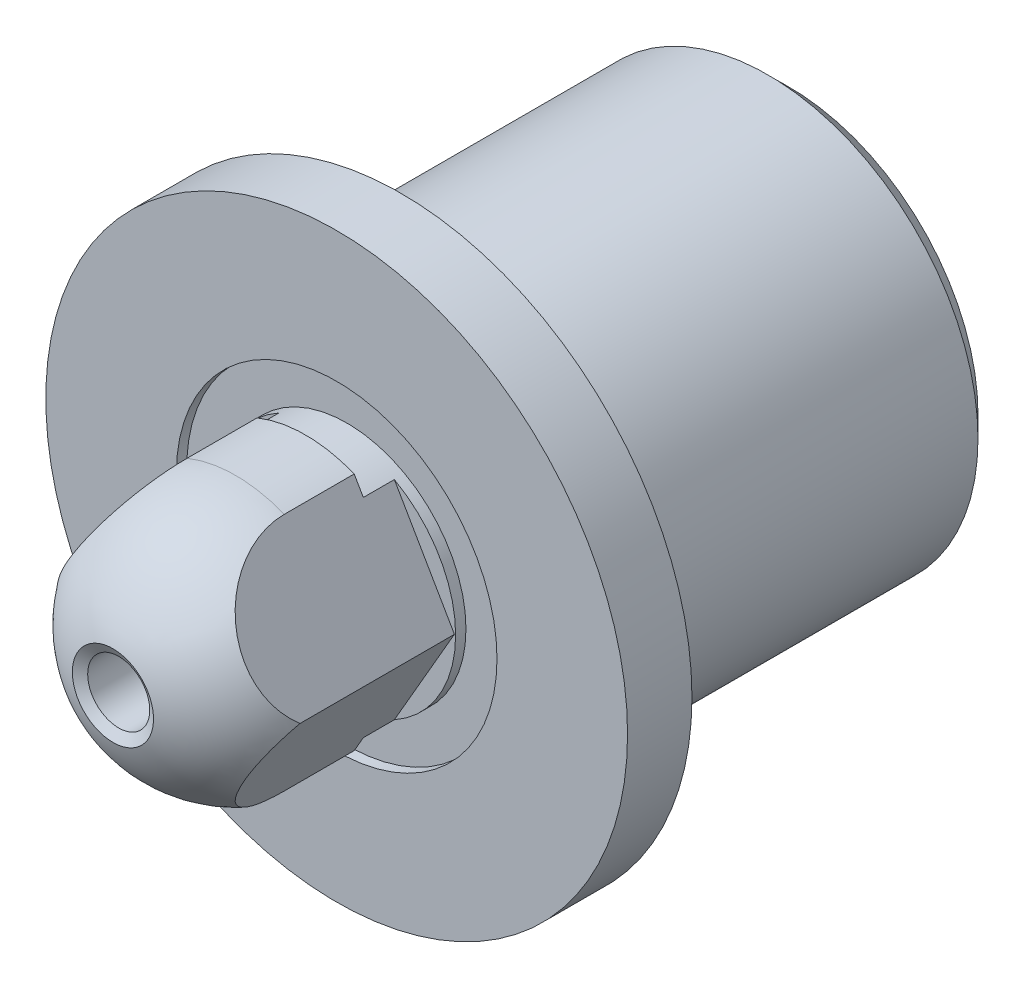
SolidWorks part; units mm, degrees
ref_plane "Front" through (0, 0, 0) normal (0, 0, 1) x (1, 0, 0)
ref_plane "Top" through (0, 0, 0) normal (0, 1, 0) x (1, 0, 0)
ref_plane "Right" through (0, 0, 0) normal (1, 0, 0) x (0, 0, -1)
sketch "Sketch1" plane through (0, 0, 0) normal (1, 0, 0) x (0, 0, -1)
  line L0 (0, 0) -> (-16.6687, 0) construction
  line L1 (0, 0) -> (37.8366, 0) construction
  line L2 (0, 0) -> (0, -30.2693) construction
  line L3 (0, 0) -> (0, 5.1594)
  line L4 (0, 5.1594) -> (-9.525, 5.1594)
  line L5 (-9.525, 5.1594) -> (-9.525, 7.1437)
  line L6 (-9.525, 7.1437) -> (-11.1061, 7.1437)
  line L7 (-11.1061, 7.1437) -> (-11.1061, 3.175)
  line L8 (-11.1061, 3.175) -> (-13.5865, 3.175)
  line L9 (-16.6687, 0) -> (-16.6687, -15.5339) construction
  line L10 (-8.3808, 0) -> (-8.3808, -24.0717) construction
  line L11 (-9.779, 5.9214) -> (-9.525, 5.9214) construction
  line L12 (-11.1061, 3.937) -> (-10.8521, 3.937) construction
  line L13 (-11.8681, 3.175) -> (-11.8681, 2.921) construction
  line L14 (-11.8681, 2.921) -> (-10.8521, 2.921) construction
  line L15 (-10.8521, 3.937) -> (-10.8521, 2.921) construction
  line L16 (-16.6687, 0) -> (-16.6687, 0.762) construction
  line L17 (-16.6687, 0) -> (-16.7615, 0) construction
  line L18 (-16.7615, 0) -> (-16.7615, -0.6279) construction
  line L19 (-8.763, 5.1594) -> (-8.763, 4.9054) construction
  line L20 (-8.763, 4.9054) -> (-9.779, 4.9054) construction
  line L21 (-9.779, 5.9214) -> (-9.779, 4.9054) construction
  line L22 (-16.7615, 0) -> (0, 0)
  arc A0 (-13.5865, 3.175) -> (-16.7615, 0) centre (-13.5865, 0) ccw
  dimension "D" = 16.6687
  dimension "B" = 10.3187
  dimension "C" = 5.5626
  dimension "E" = 9.525
  dimension "A" = 6.35
  dimension "F" = 14.2875
  dimension "D7" = 0.254
  dimension "D8" = 1.016
ref_axis "Axis1" through (0, 0, 17.3335) along (0, 0, -1)
revolve "Revolve1" add sketch "Sketch1" angle 360 about axis through (0, 0, 17.3335) along (0, 0, -1)
sketch "Sketch3" plane through (0, 0, 0) normal (1, 0, 0) x (0, 0, -1)
  line L1 (-11.8681, 2.921) -> (-10.8521, 2.921)
  line L2 (-11.8681, 2.921) -> (-11.8681, 3.937)
  line L3 (-11.8681, 3.937) -> (-10.8521, 3.937)
  line L4 (-10.8521, 2.921) -> (-10.8521, 3.937)
  line L5 (-9.779, 5.9214) -> (-8.763, 5.9214)
  line L6 (-9.779, 5.9214) -> (-9.779, 4.9054)
  line L7 (-9.779, 4.9054) -> (-8.763, 4.9054)
  line L8 (-8.763, 5.9214) -> (-8.763, 4.9054)
revolve "Cut-Revolve1" cut sketch "Sketch3" angle 360 about axis through (0, 0, 17.3335) along (0, 0, -1)
chamfer "Chamfer1" distance 0.5159 angle 45 1 edges at (5.1594, 0, 0)
sketch "Sketch2" plane through (0, 0, 0) normal (0, 0, -1) x (-1, 0, 0)
  circle A0 centre (0, 0) radius 0.762
  dimension "D1" = 1.524
extrude "Cut-Extrude1" cut sketch "Sketch2" against normal blind 2.54
ref_plane "Plane1" through (0, 0, 8.3808) normal (0, 0, 1) x (1, 0, 0)
mirror "Mirror1" about plane through (0, 0, 8.3808) normal (0, 0, 1) of "Cut-Extrude1"
chamfer "Chamfer2" distance 0.254 angle 45 2 edges at (-0.762, 0, 0) (-0.762, 0, 16.6688) first distance on face at (-0.762, 0, 0) first distance on face at (3.175, 0, 13.5865)
ref_plane "Plane2" through (0, 0, 16.7615) normal (0, 0, 1) x (1, 0, 0)
sketch "Sketch4" plane through (0, 0, 16.7615) normal (0, 0, 1) x (1, 0, 0)
  line L0 (0, 0) -> (0, 5.0834) construction
  line L1 (0, 0) -> (-5.3278, 0) construction
  line L2 (-2.8914, 0) -> (-1.0583, 3.175)
  line L3 (-1.0583, 3.175) -> (1.0583, 3.175)
  line L4 (1.0583, 3.175) -> (2.8914, 0)
  line L5 (2.8914, 0) -> (1.0583, -3.175)
  line L6 (1.0583, -3.175) -> (-1.0583, -3.175)
  line L7 (-1.0583, -3.175) -> (-2.8914, 0)
  line L8 (0, 0) -> (0, -5.885) construction
  circle A1 centre (0, 0) radius 3.175 construction
  circle A2 centre (0, 0) radius 3.175 construction
  dimension "D1" = 60
  dimension "D2" = 2.1167
extrude "Cut-Extrude2" cut sketch "Sketch4" against normal up to surface (5.6554 mm away) flip side to cut up to face at (7.1437, 0, 11.1061)
equation "\"D1@Chamfer1\" = \"B@Sketch1\"*.05"
equation "\"D2@Sketch4\" = \"A@Sketch1\"/3"
